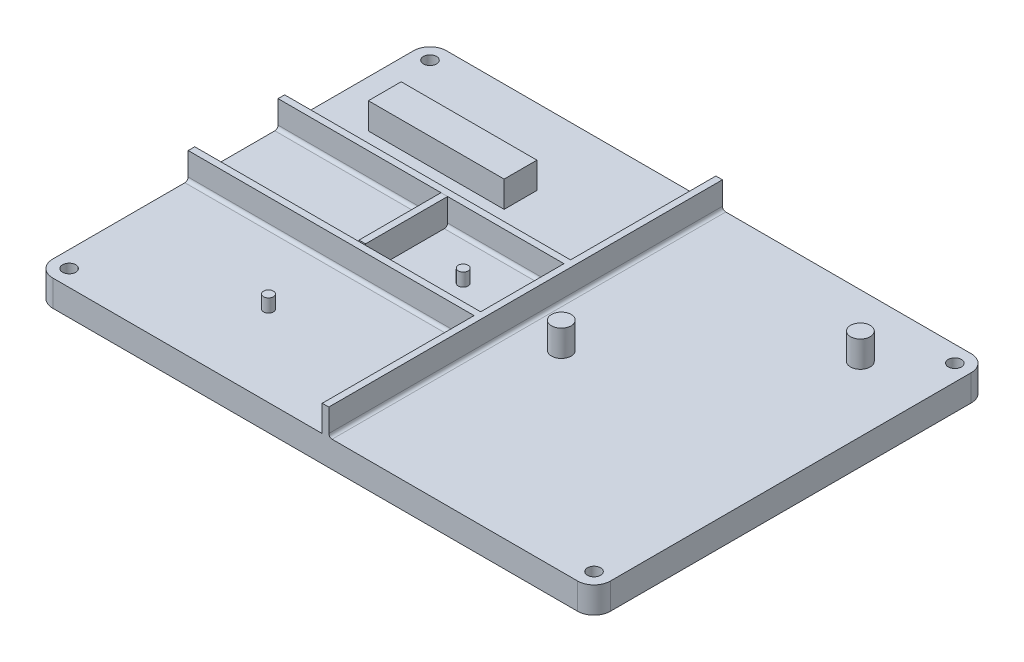
SolidWorks part; units mm, degrees
ref_plane "Front Plane" through (0, 0, 0) normal (0, 0, 1) x (1, 0, 0)
ref_plane "Top Plane" through (0, 0, 0) normal (0, 1, 0) x (1, 0, 0)
ref_plane "Right Plane" through (0, 0, 0) normal (1, 0, 0) x (0, 0, -1)
sketch "Sketch1" plane through (0, 0, 0) normal (0, 1, 0) x (1, 0, 0)
  line L1 (85, -60) -> (-85, -60)
  line L2 (85, -60) -> (85, 60)
  line L3 (85, 60) -> (-85, 60)
  line L4 (-85, -60) -> (-85, 60)
  line L5 (85, -60) -> (-85, 60) construction
  line L6 (85, 60) -> (-85, -60) construction
  point P0 (0, 0)
  dimension "D1" = 170
  dimension "D2" = 120
extrude "Boss-Extrude1" add sketch "Sketch1" along normal blind 8 contours L2 L1 L4 L3
sketch "Sketch2" plane through (-17.7915, 8, -3.068) normal (0, 1, 0) x (1, 0, 0)
  line L1 (-52.8988, 33.84) -> (-11.5182, 33.84)
  line L2 (-52.8988, 33.84) -> (-52.8988, 23.84)
  line L3 (-52.8988, 23.84) -> (-11.5182, 23.84)
  line L4 (-11.5182, 33.84) -> (-11.5182, 23.84)
  line L5 (-52.8988, 33.84) -> (-11.5182, 23.84) construction
  line L6 (-52.8988, 23.84) -> (-11.5182, 33.84) construction
  point P0 (-32.2085, 28.84)
  dimension "D1" = 10
extrude "Boss-Extrude2" add sketch "Sketch2" along normal blind 8 contours L2 L1 L4 L3
sketch "Sketch3" plane through (0, 8, 0) normal (0, 1, 0) x (1, 0, 0)
  line L0 (-85, -60) -> (-85, 60) construction
  line L1 (85, 60) -> (-85, 60) construction
  line L2 (85, -60) -> (-85, -60) construction
  line L3 (85, -60) -> (85, 60) construction
  circle A0 centre (-80, 55) radius 2
  circle A1 centre (-80, -55) radius 2
  circle A2 centre (80, 55) radius 2
  circle A3 centre (80, -55) radius 2
  dimension "D1" = 5
  dimension "D3" = 5
  dimension "D7" = 5
  dimension "D2" = 5
  dimension "D4" = 5
  dimension "D5" = 5
  dimension "D6" = 5
  dimension "D8" = 5
extrude "Cut-Extrude1" cut sketch "Sketch3" against normal blind 8
sketch "Sketch7" plane through (12.7031, 8, 3.5658) normal (0, 1, 0) x (1, 0, 0)
  circle A0 centre (52.4005, 44.6595) radius 3
  point P2 (0, 0)
  point P3 (0, 0)
  point P4 (0, 0)
  point P5 (0, 0)
extrude "Boss-Extrude3" add sketch "Sketch7" along normal blind 8 contours A0
sketch "Sketch8" plane through (0, 16, 3.5658) normal (0, 1, 0) x (1, 0, 0)
  circle A0 centre (65.1036, 44.6595) radius 1.5
  point P3 (0, 0)
  point P4 (0, 0)
  point P5 (0, 0)
  point P6 (0, 0)
  point P7 (0, 0)
extrude "Boss-Extrude6" add sketch "Sketch8" against normal blind 4 contours A0
sketch "Sketch9" plane through (0, 16, 3.5658) normal (0, 1, 0) x (1, 0, 0)
  circle A0 centre (64.9051, 44.2737) radius 1.5
  point P2 (0, 0)
extrude "Boss-Extrude7" add sketch "Sketch9" against normal blind 4
sketch "Sketch10" plane through (-8.7547, 8, 20.4679) normal (0, 1, 0) x (1, 0, 0)
  circle A0 centre (25.4063, 18.8562) radius 3
extrude "Boss-Extrude8" add sketch "Sketch10" along normal blind 8
sketch "Sketch11" plane through (4.1485, 8, 0) normal (0, 1, 0) x (1, 0, 0)
  line L5 (-2, 60) -> (0, 60)
  line L6 (-2, 60) -> (-2, -60)
  line L7 (-2, -60) -> (0, -60)
  line L8 (0, 60) -> (0, -60)
  point P6 (0, 0)
  point P7 (0, 60)
  dimension "D1" = 2
extrude "Boss-Extrude9" add sketch "Sketch11" along normal blind 8
sketch "Sketch13" plane through (0, 8, 0) normal (0, 1, 0) x (1, 0, 0)
  line L0 (-85, -60) -> (-85, 60) construction
  line L1 (-85, 15.6956) -> (2.1485, 15.6956)
  line L2 (-85, 15.6956) -> (-85, 13.6956)
  line L3 (-85, 13.6956) -> (2.1485, 13.6956)
  line L4 (2.1485, 15.6956) -> (2.1485, 13.6956)
  line L5 (2.1485, 60) -> (2.1485, -60) construction
  dimension "D1" = 2
extrude "Boss-Extrude10" add sketch "Sketch13" along normal blind 8 contours L3 L4 L1 L2
extrude "Boss-Extrude11" add sketch "Sketch7<3>" against normal blind 1.2897
sketch "Sketch7<3>" plane through (12.7031, 8, 3.5658) normal (0, 1, 0) x (1, 0, 0) same geometry as "Sketch7"
sketch "Sketch14" plane through (0, 16, 0) normal (0, 1, 0) x (1, 0, 0)
  line L0 (-85, 13.6956) -> (2.1485, 13.6956) construction
  line L1 (-35.3306, 13.6956) -> (-33.3306, 13.6956)
  line L2 (-35.3306, 13.6956) -> (-35.3306, -11.3044)
  line L3 (-35.3306, -11.3044) -> (-33.3306, -11.3044)
  line L4 (-33.3306, 13.6956) -> (-33.3306, -11.3044)
  line L5 (-85, -60) -> (-85, 13.6956) construction
  line L6 (-33.3306, -11.3044) -> (-85, -11.3044)
  line L7 (-33.3306, -11.3044) -> (-33.3306, -13.3044)
  line L8 (-33.3306, -13.3044) -> (-85, -13.3044)
  line L9 (-85, -11.3044) -> (-85, -13.3044)
  dimension "D1" = 2
  dimension "D2" = 25
  dimension "D3" = 2
extrude "Boss-Extrude13" add sketch "Sketch14" against normal blind 8 separate body contours L3 L2 L1 L4
sketch "Sketch18" plane through (0, 8, 0) normal (0, 1, 0) x (1, 0, 0)
  line L0 (2.1485, 13.6956) -> (2.1485, -60) construction
  line L1 (2.1485, -11.7107) -> (-85, -11.7107)
  line L2 (2.1485, -11.7107) -> (2.1485, -13.7107)
  line L3 (2.1485, -13.7107) -> (-85, -13.7107)
  line L4 (-85, -11.7107) -> (-85, -13.7107)
  line L5 (-85, -60) -> (-85, 13.6956) construction
  point P8 (-2, -11.3137)
  point P9 (-2, -11.3044)
  point P10 (-2, -13.6956)
  dimension "D1" = 2
extrude "Boss-Extrude16" add sketch "Sketch18" along normal blind 8 contours L1 L4 L3 L2
sketch "Sketch19" plane through (0, 8, 0) normal (0, 1, 0) x (1, 0, 0)
  circle A0 centre (-16.0623, 1.1849) radius 1.5
  circle A1 centre (-38.9018, -35.3306) radius 1.5
  point P4 (0, 0)
  point P5 (0, 0)
  point P6 (0, 0)
  point P7 (0, 0)
extrude "Boss-Extrude17" add sketch "Sketch19" along normal blind 4
fillet "Fillet1" radius 1 7 edges at (-41.4257, 8, 13.7107) (-41.4257, 8, 11.7107) (-41.4257, 8, -13.6956) (2.1485, 8, -0.9924) (4.1485, 8, 0) (2.1485, 8, -37.8478) (-41.4257, 8, -15.6956)
fillet "Fillet6" radius 5 4 edges at (85, 4, -60) (85, 4, 60) (-85, 4, 60) (-85, 4, -60)
